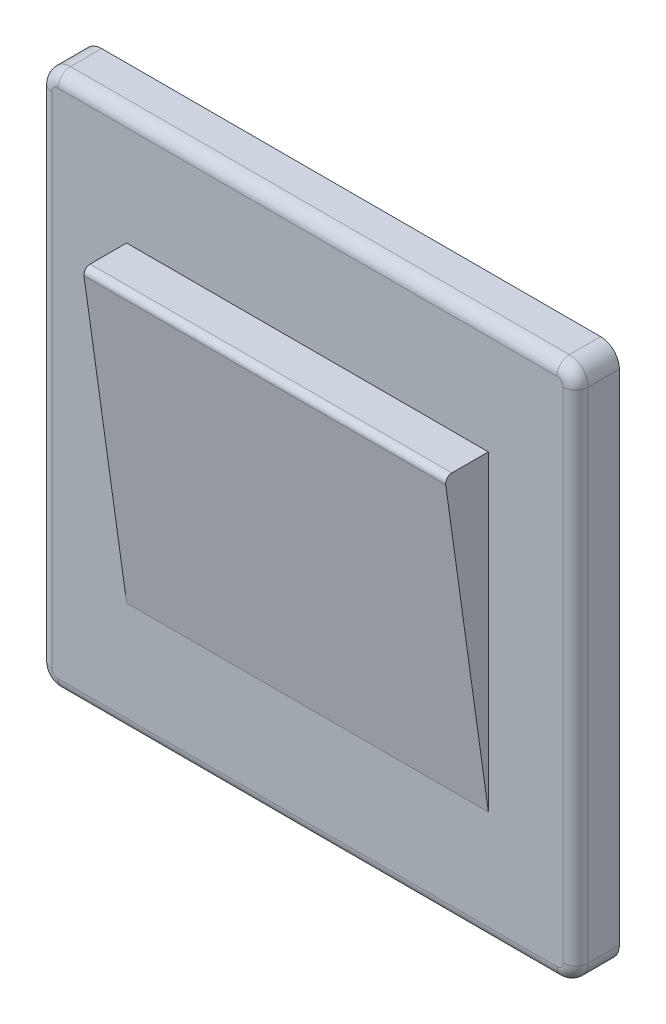
SolidWorks part; units mm, degrees
ref_plane "前视基准面" through (0, 0, 0) normal (0, 0, 1) x (1, 0, 0)
ref_plane "上视基准面" through (0, 0, 0) normal (0, 1, 0) x (1, 0, 0)
ref_plane "右视基准面" through (0, 0, 0) normal (1, 0, 0) x (0, 0, -1)
other "Configuration Table"
sketch "草图1" plane through (0, 0, 0) normal (0, 0, 1) x (1, 0, 0)
  line L1 (0, 0) -> (86, 0)
  line L2 (0, 0) -> (0, 86)
  line L3 (0, 86) -> (86, 86)
  line L4 (86, 0) -> (86, 86)
  line L5 (14, 68) -> (72, 68)
  line L6 (14, 68) -> (14, 18)
  line L7 (14, 18) -> (72, 18)
  line L8 (72, 68) -> (72, 18)
  dimension "D1" = 86
  dimension "D2" = 86
  dimension "D3" = 14
  dimension "D4" = 18
  dimension "D5" = 14
  dimension "D6" = 18
extrude "凸台-拉伸1" add sketch "草图1" along normal blind 7 contours L8 L5 L6 L7 | L1 L4 L3 L2 L5 L8 L7 L6 region at (1.2162, 43, 0) region at (43, 43, 0)
extrude "凸台-拉伸3" add sketch "草图1<5>" along normal blind 14 contours L8 L5 L6 L7 region at (43, 43, 0)
sketch "草图1<5>" plane through (0, 0, 0) normal (0, 0, 1) x (1, 0, 0) same geometry as "草图1"
sketch "草图2" plane through (14, 0, 0) normal (-1, 0, 0) x (0, 0, 1)
  line L0 (14, 68) -> (7, 18)
  line L1 (7, 18) -> (14, 18)
  line L2 (14, 18) -> (14, 68)
extrude "切除-拉伸1" cut sketch "草图2" against normal through all
fillet "圆角1" radius 3 4 edges at (86, 86, 3.5) (86, 0, 3.5) (0, 0, 3.5) (0, 86, 3.5)
fillet "圆角2" radius 1 1 edges at (43, 68, 14)
fillet "圆角3" radius 2 8 edges at (0.8787, 85.1213, 7) (0, 43, 7) (0.8787, 0.8787, 7) (43, 0, 7) (85.1213, 0.8787, 7) (86, 43, 7) (85.1213, 85.1213, 7) (43, 86, 7)
